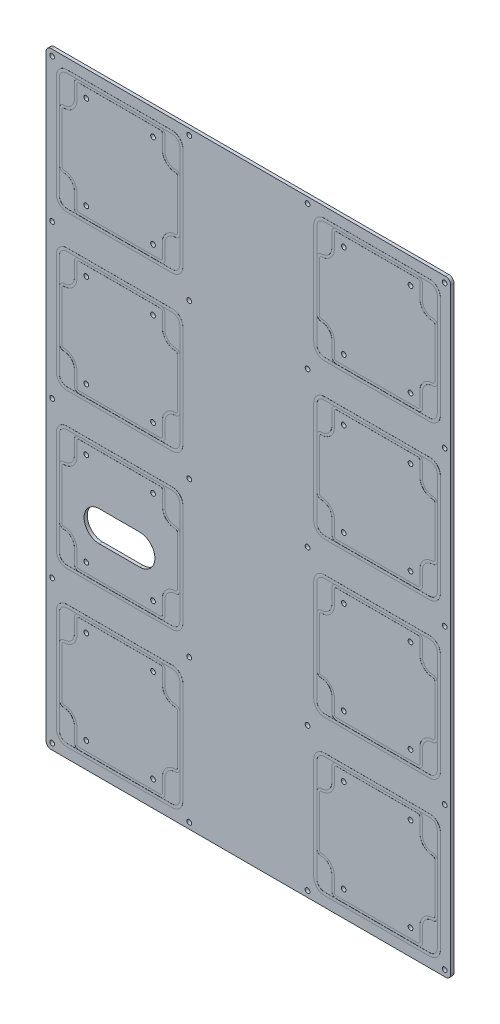
SolidWorks part; units mm, degrees
ref_plane "Front Plane" through (0, 0, 0) normal (0, 0, 1) x (1, 0, 0)
ref_plane "Top Plane" through (0, 0, 0) normal (0, 1, 0) x (1, 0, 0)
ref_plane "Right Plane" through (0, 0, 0) normal (1, 0, 0) x (0, 0, -1)
sketch "Sketch1" plane through (0, 0, 0) normal (0, 0, 1) x (1, 0, 0)
  line L1 (0, 0) -> (254, 0)
  line L2 (0, 0) -> (0, 381)
  line L3 (0, 381) -> (254, 381)
  line L4 (254, 0) -> (254, 381)
  dimension "D1" = 381
  dimension "D2" = 254
extrude "Boss-Extrude1" add sketch "Sketch1" along normal blind 2.032
sketch "Sketch2" plane through (0, 0, 2.032) normal (0, 0, 1) x (1, 0, 0)
  line L0 (89.8652, 377.19) -> (89.8652, 3.81) construction
  line L1 (0, 381) -> (254, 381) construction
  line L2 (127, 381) -> (127, 377.19) construction
  line L3 (3.81, 377.19) -> (250.19, 377.19) construction
  line L5 (164.1348, 377.19) -> (164.1348, 3.81) construction
  line L6 (3.81, 377.19) -> (3.81, 3.81) construction
  line L7 (3.81, 3.81) -> (250.19, 3.81) construction
  line L8 (250.19, 3.81) -> (250.19, 377.19) construction
  line L9 (3.81, 190.5) -> (250.19, 190.5) construction
  line L10 (3.81, 287.3756) -> (250.19, 287.3756) construction
  line L11 (3.81, 93.6244) -> (250.19, 93.6244) construction
  line L12 (0, 381) -> (0, 0) construction
  line L13 (0, 190.5) -> (3.81, 190.5) construction
  circle A0 centre (3.81, 377.19) radius 1.4732
  circle A1 centre (89.8652, 377.19) radius 1.4732
  circle A2 centre (164.1348, 377.19) radius 1.4732
  circle A3 centre (250.19, 377.19) radius 1.4732
  circle A4 centre (164.1348, 287.3755) radius 1.4732
  circle A5 centre (3.81, 287.3756) radius 1.4732
  circle A6 centre (250.19, 287.3756) radius 1.4732
  circle A7 centre (89.8652, 287.3756) radius 1.4732
  circle A8 centre (164.1348, 190.5) radius 1.4732
  circle A9 centre (3.81, 191.135) radius 1.4732
  circle A10 centre (250.19, 190.5) radius 1.4732
  circle A11 centre (89.8652, 190.5) radius 1.4732
  circle A12 centre (164.1348, 93.6244) radius 1.4732
  circle A13 centre (3.81, 93.6244) radius 1.4732
  circle A14 centre (250.19, 93.6244) radius 1.4732
  circle A15 centre (89.8652, 93.6244) radius 1.4732
  circle A16 centre (164.1348, 3.81) radius 1.4732
  circle A17 centre (3.81, 3.81) radius 1.4732
  circle A18 centre (250.19, 3.81) radius 1.4732
  circle A19 centre (89.8652, 3.81) radius 1.4732
  dimension "D6" = 2.9464
  dimension "D23" = 0
  dimension "D24" = 0
  dimension "D25" = 0
  dimension "D28" = 0
  dimension "D29" = 0
  dimension "D30" = 0
  dimension "D31" = 0
  dimension "D32" = 86.0552
  dimension "D1" = 246.38
  dimension "D3" = 373.38
  dimension "D4" = 96.8756
  dimension "D5" = 96.8756
  dimension "D7" = 86.0552
  dimension "D8" = 86.0552
  dimension "D9" = 0
  dimension "D10" = 0
  dimension "D11" = 0
  dimension "D12" = 86.0552
  dimension "D13" = 0
  dimension "D14" = 0
  dimension "D15" = 0
  dimension "D16" = 0
  dimension "D17" = 0
  dimension "D18" = 0
  dimension "D19" = 0
  dimension "D20" = 0
  dimension "D21" = 0
  dimension "D22" = 0
  dimension "D26" = 0
  dimension "D27" = 0
extrude "Cut-Extrude1" cut sketch "Sketch2" against normal through all
fillet "Fillet1" radius 3.175 4 edges at (254, 0, 1.016) (0, 0, 1.016) (254, 381, 1.016) (0, 381, 1.016)
sketch "Sketch3" plane through (0, 0, 2.032) normal (0, 0, 1) x (1, 0, 0)
  line L0 (9.9695, 45.1866) -> (46.2026, 45.1866) construction
  line L1 (46.2026, 45.1866) -> (46.2026, 9.9695) construction
  line L2 (81.2038, 28.3591) -> (82.4357, 28.3591) construction
  line L3 (82.4357, 29.591) -> (82.4357, 60.7822)
  line L4 (73.0377, 11.2014) -> (73.0377, 20.193)
  line L5 (81.2038, 62.0141) -> (82.4357, 62.0141) construction
  line L6 (71.8058, 9.9695) -> (20.5994, 9.9695)
  line L7 (19.3675, 11.2014) -> (19.3675, 20.193)
  line L8 (11.2014, 28.3591) -> (9.9695, 28.3591) construction
  line L9 (9.9695, 29.591) -> (9.9695, 60.7822)
  line L10 (73.0377, 79.1718) -> (73.0377, 70.1802)
  line L11 (71.8058, 80.4037) -> (20.5994, 80.4037)
  line L12 (3.175, 0) -> (250.825, 0) construction
  line L13 (0, 377.825) -> (0, 3.175) construction
  line L14 (11.2014, 62.0141) -> (9.9695, 62.0141) construction
  line L15 (19.3675, 79.1718) -> (19.3675, 70.1802)
  line L16 (17.78, 79.1718) -> (17.78, 70.1802)
  line L17 (8.382, 29.591) -> (8.382, 60.7822)
  line L18 (17.78, 11.2014) -> (17.78, 20.193)
  line L19 (71.8058, 8.382) -> (20.5994, 8.382)
  line L20 (74.6252, 11.2014) -> (74.6252, 20.193)
  line L21 (84.0232, 29.591) -> (84.0232, 60.7822)
  line L22 (74.6252, 79.1718) -> (74.6252, 70.1802)
  line L23 (71.8058, 81.9912) -> (20.5994, 81.9912)
  arc A0 (19.3675, 20.193) -> (11.2014, 28.3591) centre (11.2014, 20.193) ccw
  arc A1 (9.9695, 29.591) -> (11.2014, 28.3591) centre (11.2014, 29.591) ccw
  arc A2 (19.3675, 11.2014) -> (20.5994, 9.9695) centre (20.5994, 11.2014) ccw
  arc A3 (73.0377, 11.2014) -> (71.8058, 9.9695) centre (71.8058, 11.2014) cw
  arc A4 (82.4357, 29.591) -> (81.2038, 28.3591) centre (81.2038, 29.591) cw
  arc A5 (73.0377, 20.193) -> (81.2038, 28.3591) centre (81.2038, 20.193) cw
  arc A6 (73.0377, 70.1802) -> (81.2038, 62.0141) centre (81.2038, 70.1802) ccw
  arc A7 (82.4357, 60.7822) -> (81.2038, 62.0141) centre (81.2038, 60.7822) ccw
  arc A8 (73.0377, 79.1718) -> (71.8058, 80.4037) centre (71.8058, 79.1718) ccw
  arc A9 (19.3675, 79.1718) -> (20.5994, 80.4037) centre (20.5994, 79.1718) cw
  arc A10 (9.9695, 60.7822) -> (11.2014, 62.0141) centre (11.2014, 60.7822) cw
  arc A11 (19.3675, 70.1802) -> (11.2014, 62.0141) centre (11.2014, 70.1802) cw
  arc A12 (17.78, 70.1802) -> (11.2014, 63.6016) centre (11.2014, 70.1802) cw
  arc A13 (8.382, 60.7822) -> (11.2014, 63.6016) centre (11.2014, 60.7822) cw
  arc A14 (8.382, 29.591) -> (11.2014, 26.7716) centre (11.2014, 29.591) ccw
  arc A15 (17.78, 20.193) -> (11.2014, 26.7716) centre (11.2014, 20.193) ccw
  arc A16 (17.78, 11.2014) -> (20.5994, 8.382) centre (20.5994, 11.2014) ccw
  arc A17 (74.6252, 11.2014) -> (71.8058, 8.382) centre (71.8058, 11.2014) cw
  arc A18 (74.6252, 20.193) -> (81.2038, 26.7716) centre (81.2038, 20.193) cw
  arc A19 (84.0232, 29.591) -> (81.2038, 26.7716) centre (81.2038, 29.591) cw
  arc A20 (84.0232, 60.7822) -> (81.2038, 63.6016) centre (81.2038, 60.7822) ccw
  arc A21 (74.6252, 70.1802) -> (81.2038, 63.6016) centre (81.2038, 70.1802) ccw
  arc A22 (74.6252, 79.1718) -> (71.8058, 81.9912) centre (71.8058, 79.1718) ccw
  arc A23 (17.78, 79.1718) -> (20.5994, 81.9912) centre (20.5994, 79.1718) cw
  point P35 (82.4357, 45.1866)
  dimension "D6" = 8.1661
  dimension "D7" = 2.4638
  dimension "D8" = 1.2319
  dimension "D1" = 9.9695
  dimension "D2" = 9.9695
  dimension "D3" = 19.3675
  dimension "D4" = 28.3591
  dimension "D5" = 45.1866
  dimension "D10" = 46.2026
  dimension "D9" = 1.5875
extrude "Cut-Extrude2" cut sketch "Sketch3" against normal blind 0.0508
sketch "Sketch4" plane through (0, 0, 2.032) normal (0, 0, 1) x (1, 0, 0)
  line L0 (8.382, 60.7822) -> (8.382, 77.2287)
  line L1 (13.1445, 81.9912) -> (20.5994, 81.9912)
  line L2 (20.5994, 81.9912) -> (79.2607, 81.9912)
  line L3 (84.0232, 77.2287) -> (84.0232, 13.1445)
  line L4 (79.2607, 8.382) -> (13.1445, 8.382)
  line L5 (8.382, 13.1445) -> (8.382, 60.7822)
  line L6 (6.477, 60.7822) -> (6.477, 77.2287)
  line L7 (13.1445, 83.8962) -> (20.5994, 83.8962)
  line L8 (20.5994, 83.8962) -> (79.2607, 83.8962)
  line L9 (85.9282, 77.2287) -> (85.9282, 13.1445)
  line L10 (79.2607, 6.477) -> (13.1445, 6.477)
  line L11 (6.477, 13.1445) -> (6.477, 60.7822)
  arc A0 (13.1445, 81.9912) -> (8.382, 77.2287) centre (13.1445, 77.2287) ccw
  arc A1 (79.2607, 81.9912) -> (84.0232, 77.2287) centre (79.2607, 77.2287) cw
  arc A2 (84.0232, 13.1445) -> (79.2607, 8.382) centre (79.2607, 13.1445) cw
  arc A3 (8.382, 13.1445) -> (13.1445, 8.382) centre (13.1445, 13.1445) ccw
  arc A4 (13.1445, 83.8962) -> (6.477, 77.2287) centre (13.1445, 77.2287) ccw
  arc A5 (79.2607, 83.8962) -> (85.9282, 77.2287) centre (79.2607, 77.2287) cw
  arc A6 (85.9282, 13.1445) -> (79.2607, 6.477) centre (79.2607, 13.1445) cw
  arc A7 (6.477, 13.1445) -> (13.1445, 6.477) centre (13.1445, 13.1445) ccw
  dimension "D1" = 4.7625
  dimension "D2" = 1.905
extrude "Boss-Extrude2" add sketch "Sketch4" along normal blind 0.0508
sketch "Sketch5" plane through (0, 0, 2.032) normal (0, 0, 1) x (1, 0, 0)
  line L0 (9.9695, 45.1866) -> (82.4357, 45.1866) construction
  line L1 (9.9695, 60.7822) -> (9.9695, 29.591) construction
  line L2 (82.4357, 29.591) -> (82.4357, 60.7822) construction
  line L3 (82.4357, 45.1866) -> (46.2026, 45.1866) construction
  line L4 (46.2026, 45.1866) -> (46.2026, 80.4037) construction
  line L5 (71.8058, 80.4037) -> (20.5994, 80.4037) construction
  circle A0 centre (25.2476, 74.3966) radius 1.4732
  circle A1 centre (67.1576, 74.3966) radius 1.4732
  circle A2 centre (67.1576, 15.9766) radius 1.4732
  circle A3 centre (25.2476, 15.9766) radius 1.4732
  dimension "D1" = 2.9464
  dimension "D2" = 20.955
  dimension "D3" = 29.21
extrude "Cut-Extrude3" cut sketch "Sketch5" against normal through all
pattern_linear "LPattern1" count 4 spacing 96.8756 along (0, 1, 0) count 2 spacing 161.5948 along (1, 0, 0) of "Cut-Extrude2", "Boss-Extrude2", "Cut-Extrude3"
sketch "Sketch6" plane through (0, 0, 2.032) normal (0, 0, 1) x (1, 0, 0)
  line L0 (33.401, 136.4615) -> (58.801, 136.4615) construction
  line L1 (33.401, 145.9865) -> (58.801, 145.9865)
  line L2 (33.401, 126.9365) -> (58.801, 126.9365)
  line L3 (250.825, 381) -> (3.175, 381) construction
  line L4 (0, 377.825) -> (0, 3.175) construction
  line L5 (3.175, 0) -> (250.825, 0) construction
  arc A0 (33.401, 145.9865) -> (33.401, 126.9365) centre (33.401, 136.4615) ccw
  arc A1 (58.801, 126.9365) -> (58.801, 145.9865) centre (58.801, 136.4615) ccw
  point P2 (46.101, 136.4615)
  dimension "D1" = 244.5385
  dimension "D2" = 46.101
  dimension "D3" = 19.05
  dimension "D4" = 136.4615
  dimension "D5" = 33.401
  dimension "D6" = 58.801
extrude "Cut-Extrude4" cut sketch "Sketch6" against normal blind 2.54
